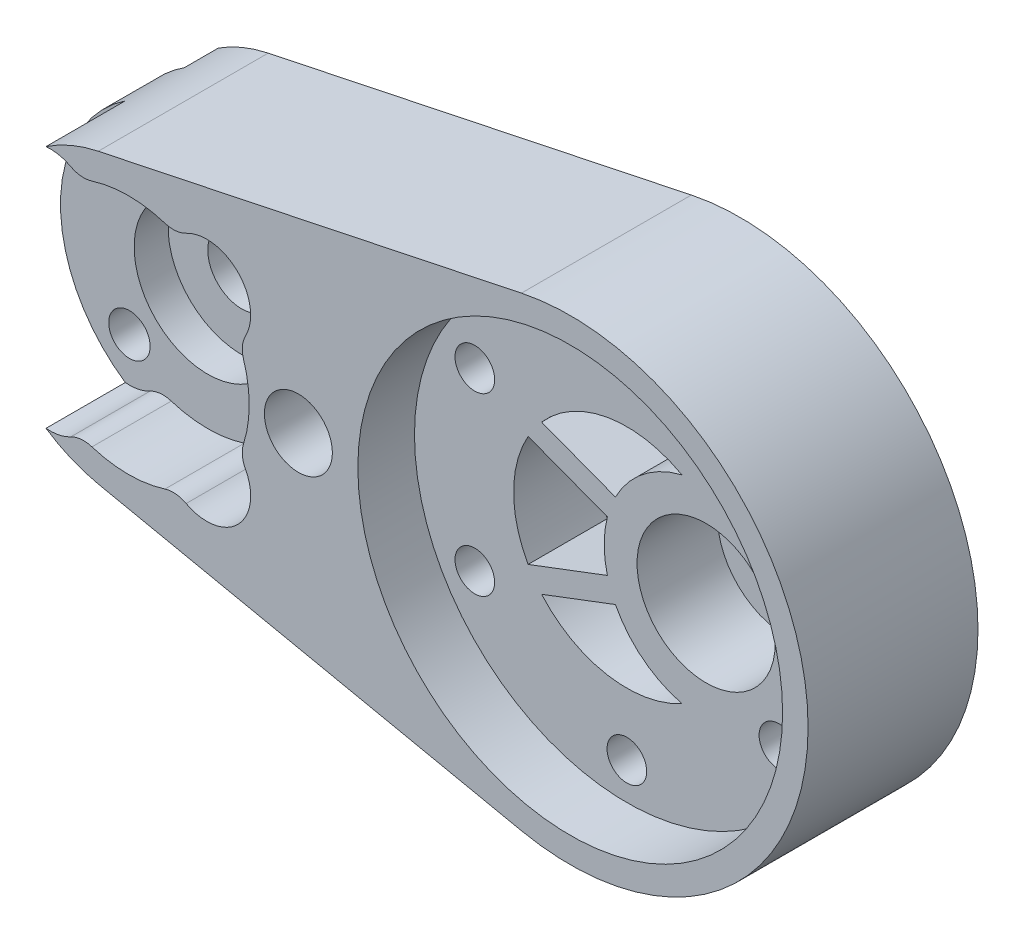
SolidWorks part; units mm, degrees
material "PLA"
ref_plane "Front Plane" through (0, 0, 0) normal (0, 0, 1) x (1, 0, 0)
ref_plane "Top Plane" through (0, 0, 0) normal (0, 1, 0) x (1, 0, 0)
ref_plane "Right Plane" through (0, 0, 0) normal (1, 0, 0) x (0, 0, -1)
sketch "layout" plane through (0, 0, 0) normal (0, 0, 1) x (1, 0, 0)
  line L0 (-87.1613, 0) -> (148.5806, 0) construction
  line L1 (0, 77.4516) -> (0, -79.4839) construction
  line L2 (-2.6667, 12.7236) -> (34.6923, 20.5534)
  line L3 (34.6923, -20.5534) -> (-2.6667, -12.7236)
  circle A0 centre (0, 0) radius 13
  circle A1 centre (39, 0) radius 21
  circle A3 centre (46, 0) radius 3
  circle A4 centre (15, 0) radius 1.5
  dimension "D1" = 7
  dimension "D2" = 42
  dimension "D3" = 26
  dimension "D4" = 46
  dimension "D5" = 6
  dimension "D6" = 31
  dimension "D7" = 3
sketch "Sketch2" plane through (0, 0, 0) normal (0, 0, 1) x (1, 0, 0)
  line L0 (-2.6667, 12.7236) -> (34.6923, 20.5534)
  line L1 (34.6923, -20.5534) -> (-2.6667, -12.7236)
  arc A0 (-2.6667, 12.7236) -> (-2.6667, -12.7236) centre (0, 0) ccw
  arc A1 (34.6923, -20.5534) -> (34.6923, 20.5534) centre (39, 0) ccw
extrude "Boss-Extrude1" add sketch "Sketch2" along normal blind 15
sketch "Sketch5" plane through (0, 0, 15) normal (0, 0, 1) x (1, 0, 0)
  line B0 (2.48, 1.6881) -> (2.48, -1.6881)
  line B1 (-16.002, 0.635) -> (-2.932, 0.635)
  line B2 (-16.002, 4.7625) -> (-16.002, 0.635)
  line B3 (-13.2056, 4.7625) -> (-16.002, 4.7625)
  line B4 (-12.573, -4.7625) -> (-12.573, -4.8306)
  line B5 (-16.002, -4.7625) -> (-12.573, -4.7625)
  line B6 (-16.002, -0.635) -> (-16.002, -4.7625)
  line B7 (-2.932, -0.635) -> (-16.002, -0.635)
  arc B8 (1.3492, -2.6795) -> (2.48, -1.6881) centre (1.48, -1.6881) ccw
  arc B9 (2.48, 1.6881) -> (1.3492, 2.6795) centre (1.48, 1.6881) ccw
  arc B10 (1.3492, 2.6795) -> (-2.932, 0.635) centre (0, 0) ccw
  arc B11 (-13.2056, 4.7625) -> (-10.2587, 7.3504) centre (-13.2056, 7.7343) ccw
  arc B12 (-5.329, 9.8908) -> (-10.2587, 7.3504) centre (-6.9148, 6.9148) ccw
  arc B13 (-5.329, 9.8908) -> (-3.0721, 9.6844) centre (-3.9553, 12.4687) ccw
  arc B14 (3.0721, 9.6844) -> (-3.0721, 9.6844) centre (0, 0) ccw
  arc B15 (3.0721, 9.6844) -> (5.329, 9.8908) centre (3.9553, 12.4687) ccw
  arc B16 (9.8908, 5.329) -> (5.329, 9.8908) centre (6.9148, 6.9148) ccw
  arc B17 (9.8908, 5.329) -> (9.6844, 3.0721) centre (12.4687, 3.9553) ccw
  arc B18 (9.6844, -3.0721) -> (9.6844, 3.0721) centre (0, 0) ccw
  arc B19 (9.6844, -3.0721) -> (9.8908, -5.329) centre (12.4687, -3.9553) ccw
  arc B20 (5.329, -9.8908) -> (9.8908, -5.329) centre (6.9148, -6.9148) ccw
  arc B21 (5.329, -9.8908) -> (3.0721, -9.6844) centre (3.9553, -12.4687) ccw
  arc B22 (-3.0721, -9.6844) -> (3.0721, -9.6844) centre (0, 0) ccw
  arc B23 (-3.0721, -9.6844) -> (-5.329, -9.8908) centre (-3.9553, -12.4687) ccw
  arc B24 (-10.2587, -7.3504) -> (-5.329, -9.8908) centre (-6.9148, -6.9148) ccw
  arc B25 (-10.2587, -7.3504) -> (-12.573, -4.8306) centre (-13.2056, -7.7343) ccw
  arc B26 (-2.932, -0.635) -> (1.3492, -2.6795) centre (0, 0) ccw
sketch_block_instance "Block1-1"
sketch_block "Block1"
sketch "Sketch6" plane through (0, 0, 15) normal (0, 0, 1) x (1, 0, 0)
  line L5 (6.9148, 6.9148) -> (-6.9148, 6.9148) construction
  line L6 (-6.9148, 6.9148) -> (-6.9148, -6.9148) construction
  line L7 (-6.9148, -6.9148) -> (6.9148, -6.9148) construction
  line L8 (6.9148, -6.9148) -> (6.9148, 6.9148) construction
  circle A0 centre (0, 0) radius 3
  circle A2 centre (0, 0) radius 9.779 construction
  circle A3 centre (-6.9148, 6.9148) radius 1.8288
  circle A4 centre (6.9148, 6.9148) radius 1.8288
  circle A5 centre (6.9148, -6.9148) radius 1.8288
  circle A6 centre (-6.9148, -6.9148) radius 1.8288
  dimension "D1" = 3.6576
  dimension "D2" = 19.558
  dimension "D3" = 6
extrude "hub mount hole pattern" cut sketch "Sketch6" against normal through all
sketch "Sketch7" plane through (0, 0, 15) normal (0, 0, 1) x (1, 0, 0)
  line L1 (25.5766, 7.75) -> (25.5766, -7.75) construction
  line L2 (25.5766, -7.75) -> (39, -15.5) construction
  line L3 (39, -15.5) -> (52.4234, -7.75) construction
  line L4 (52.4234, -7.75) -> (52.4234, 7.75) construction
  line L5 (52.4234, 7.75) -> (39, 15.5) construction
  line L6 (39, 15.5) -> (25.5766, 7.75) construction
  circle A0 centre (39, 0) radius 15.5 construction
  circle A1 centre (25.5766, 7.75) radius 1.75
  circle A2 centre (39, 15.5) radius 1.75
  circle A3 centre (52.4234, 7.75) radius 1.75
  circle A4 centre (52.4234, -7.75) radius 1.75
  circle A5 centre (39, -15.5) radius 1.75
  circle A6 centre (25.5766, -7.75) radius 1.75
  circle A7 centre (46, 0) radius 3.25
  dimension "D1" = 3.5
  dimension "D2" = 6.5
  dimension "D3" = 31
extrude "motor hole pattern" cut sketch "Sketch7" against normal through all
sketch "Sketch8" plane through (0, 0, 15) normal (0, 0, 1) x (1, 0, 0)
  circle A0 centre (39, 0) radius 18.75
  dimension "D1" = 37.5
extrude "motor cutout" cut sketch "Sketch8" against normal blind 5
sketch "Sketch9" plane through (0, 0, 15) normal (0, 0, 1) x (1, 0, 0)
  arc A0 (-7.2811, 10.7696) -> (-7.2811, -10.7696) centre (0, 0) ccw
  arc A156 (-10.7546, -7.415) -> (-5.0938, -10.3321) centre (-6.9148, -6.9148) ccw
  arc A157 (-3.2233, -10.161) -> (-5.0938, -10.3321) centre (-3.9553, -12.4687) ccw
  arc A158 (-3.2233, -10.161) -> (3.2233, -10.161) centre (0, 0) ccw
  arc A159 (5.0938, -10.3321) -> (3.2233, -10.161) centre (3.9553, -12.4687) ccw
  arc A160 (10.161, -3.2233) -> (10.3321, -5.0938) centre (12.4687, -3.9553) ccw
  arc A161 (5.0938, -10.3321) -> (10.3321, -5.0938) centre (6.9148, -6.9148) ccw
  arc A162 (10.161, -3.2233) -> (10.161, 3.2233) centre (0, 0) ccw
  arc A163 (10.3321, 5.0938) -> (10.161, 3.2233) centre (12.4687, 3.9553) ccw
  arc A164 (10.3321, 5.0938) -> (5.0938, 10.3321) centre (6.9148, 6.9148) ccw
  arc A165 (3.2233, 10.161) -> (5.0938, 10.3321) centre (3.9553, 12.4687) ccw
  arc A166 (-5.0938, 10.3321) -> (-10.7546, 7.415) centre (-6.9148, 6.9148) ccw
  arc A167 (-5.0938, 10.3321) -> (-3.2233, 10.161) centre (-3.9553, 12.4687) ccw
  arc A168 (3.2233, 10.161) -> (-3.2233, 10.161) centre (0, 0) ccw
  arc A169 (-7.2811, -10.7696) -> (-5.0938, -10.3321) centre (-6.9148, -6.9148) ccw
  arc A170 (-3.2233, -10.161) -> (-5.0938, -10.3321) centre (-3.9553, -12.4687) ccw
  arc A171 (-3.2233, -10.161) -> (3.2233, -10.161) centre (0, 0) ccw
  arc A172 (5.0938, -10.3321) -> (3.2233, -10.161) centre (3.9553, -12.4687) ccw
  arc A173 (10.161, -3.2233) -> (10.3321, -5.0938) centre (12.4687, -3.9553) ccw
  arc A174 (5.0938, -10.3321) -> (10.3321, -5.0938) centre (6.9148, -6.9148) ccw
  arc A175 (10.161, -3.2233) -> (10.161, 3.2233) centre (0, 0) ccw
  arc A176 (10.3321, 5.0938) -> (10.161, 3.2233) centre (12.4687, 3.9553) ccw
  arc A177 (10.3321, 5.0938) -> (5.0938, 10.3321) centre (6.9148, 6.9148) ccw
  arc A178 (3.2233, 10.161) -> (5.0938, 10.3321) centre (3.9553, 12.4687) ccw
  arc A179 (-5.0938, 10.3321) -> (-7.2811, 10.7696) centre (-6.9148, 6.9148) ccw
  arc A180 (-5.0938, 10.3321) -> (-3.2233, 10.161) centre (-3.9553, 12.4687) ccw
  arc A181 (3.2233, 10.161) -> (-3.2233, 10.161) centre (0, 0) ccw
  dimension "D1" = 0.5
extrude "hub mount cutout" cut sketch "Sketch9" against normal blind 7
sketch "Sketch10" plane through (0, 0, 0) normal (0, 0, -1) x (-1, 0, 0)
  circle A0 centre (-15, 0) radius 5
  dimension "D1" = 10
extrude "Boss-Extrude2" add sketch "Sketch10" along normal blind 5.5
sketch "Sketch12" plane through (0, 0, 0) normal (0, 0, 1) x (1, 0, 0)
  circle A0 centre (15, 0) radius 1.55
  dimension "D1" = 3.1
extrude "Linkage pin hole" cut sketch "Sketch12" against normal through all both and the other way through all
chamfer "Chamfer1" distance 2.75 angle 45 1 edges at (10, 0, -5.5)
sketch "Sketch13" plane through (0, 0, 10) normal (0, 0, 1) x (1, 0, 0)
  circle A0 centre (46, 0) radius 6.1
  dimension "D1" = 12.2
extrude "Cut-Extrude7" cut sketch "Sketch13" against normal blind 7.1
sketch "Sketch14" plane through (0, 0, 8) normal (0, 0, 1) x (1, 0, 0)
  circle A0 centre (0, 0) radius 6.5
  dimension "D1" = 13
extrude "Cut-Extrude8" cut sketch "Sketch14" against normal blind 3
sketch "Sketch15" plane through (0, 0, 0) normal (0, 0, -1) x (-1, 0, 0)
  circle A0 centre (-25.5766, -7.75) radius 3.5
  circle A1 centre (-39, -15.5) radius 3.5
  circle A2 centre (-52.4234, -7.75) radius 3.5
  circle A3 centre (-52.4234, 7.75) radius 3.5
  circle A4 centre (-39, 15.5) radius 3.5
  circle A5 centre (-25.5766, 7.75) radius 3.5
  dimension "D1" = 7
extrude "Cut-Extrude9" cut sketch "Sketch15" against normal offset from surface (5 mm away) 5 up to face at (52.1, 0, 10)
sketch "Sketch16" plane through (0, 0, 8) normal (0, 0, 1) x (1, 0, 0)
  circle A0 centre (15, 0) radius 3
  dimension "D1" = 6
extrude "Cut-Extrude10" cut sketch "Sketch16" against normal offset from surface 10.5 and the other way through all up to face at (12.75, 0, -5.5)
sketch "Sketch17" plane through (0, 0, 10) normal (0, 0, 1) x (1, 0, 0)
  arc A0 (43.8571, 8.7412) -> (43.8571, -8.7412) centre (39, 0) ccw
  arc A1 (43.8571, 8.7412) -> (43.8571, -8.7412) centre (46, 0) ccw
  dimension "D1" = 9
  dimension "D2" = 10
extrude "Cut-Extrude12" cut sketch "Sketch17" against normal offset from surface (7 mm away) 3 up to face at (22.0766, 7.75, 0)
sketch "Sketch18" plane through (0, 0, 10) normal (0, 0, 1) x (1, 0, 0)
  line L0 (25.5766, -7.75) -> (46, 0) construction
  line L1 (25.5766, 7.75) -> (46, 0) construction
  line L2 (31.472, -6.5825) -> (37.9923, -4.1082)
  line L3 (31.472, 6.5825) -> (37.9923, 4.1082)
  line L4 (30.2803, -4.8955) -> (37.2828, -2.2383)
  line L5 (30.2803, 4.8955) -> (37.2828, 2.2383)
  line L6 (25.9314, -8.6849) -> (48.8186, 0) construction
  line L7 (25.2218, -6.8151) -> (43.1814, 0) construction
  line L8 (25.9314, 8.6849) -> (48.8186, 0) construction
  line L9 (25.2218, 6.8151) -> (43.1814, 0) construction
  arc A0 (43.8571, 8.7412) -> (43.8571, -8.7412) centre (39, 0) ccw construction
  arc A1 (43.8571, 8.7412) -> (43.8571, -8.7412) centre (46, 0) ccw construction
  arc A2 (31.472, 6.5825) -> (30.2803, 4.8955) centre (39, 0) ccw
  arc A3 (37.9923, 4.1082) -> (37.2828, 2.2383) centre (46, 0) ccw
  arc A5 (30.2803, -4.8955) -> (31.472, -6.5825) centre (39, 0) ccw
  arc A6 (37.2828, -2.2383) -> (37.9923, -4.1082) centre (46, 0) ccw
  dimension "D1" = 1
  dimension "D2" = 1
extrude "Boss-Extrude3" add sketch "Sketch18" against normal up to next
sketch "Sketch19" plane through (0, 0, 0) normal (0, 0, -1) x (-1, 0, 0)
  circle A0 centre (-6.9148, -6.9148) radius 4
  circle A1 centre (-6.9148, 6.9148) radius 4
  circle A2 centre (6.9148, 6.9148) radius 4
  circle A3 centre (6.9148, -6.9148) radius 4
  dimension "D1" = 8
extrude "Cut-Extrude13" cut sketch "Sketch19" against normal offset from surface 5 and the other way through all up to face at (6.5, 0, 8)
fillet "Fillet1" radius 5 1 edges at (20, 0, 0)
